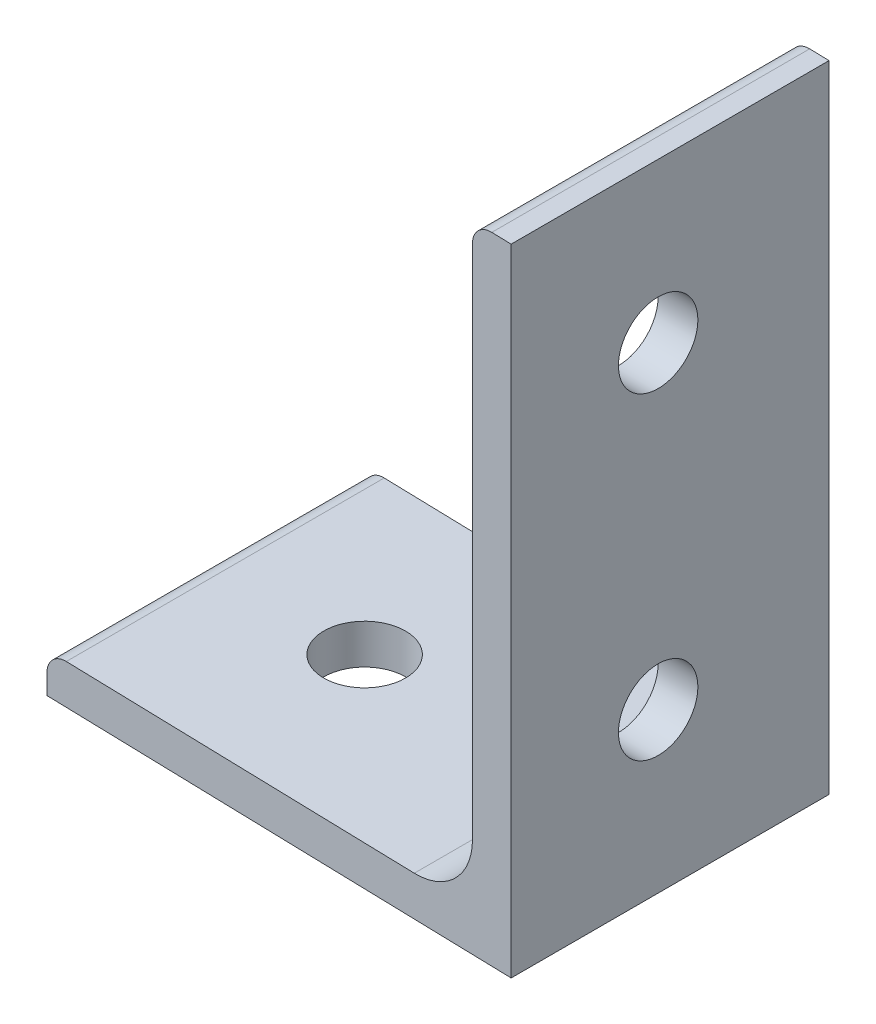
SolidWorks part; units mm, degrees
ref_plane "Front Plane" through (0, 0, 0) normal (0, 0, 1) x (1, 0, 0)
ref_plane "Top Plane" through (0, 0, 0) normal (0, 1, 0) x (1, 0, 0)
ref_plane "Right Plane" through (0, 0, 0) normal (1, 0, 0) x (0, 0, -1)
sketch "Sketch0" plane through (0, 0, 0) normal (0, 0, 1) x (1, 0, 0)
  line L0 (-19.05, -25.4) -> (19.05, -25.4)
  line L1 (19.05, -25.4) -> (19.05, 25.4)
  line L2 (19.05, 0) -> (0, 0) construction
  line L3 (0, 0) -> (0, -25.4) construction
  line L4 (15.875, -17.4498) -> (15.875, 25.4) construction
  line L5 (11.0998, -22.225) -> (-19.05, -22.225) construction
  arc A0 (15.875, -17.4498) -> (11.0998, -22.225) centre (11.0998, -17.4498) cw
  point P3 (14.4764, -20.8264)
  dimension "Inside Corner Radius" = 4.7752
  dimension "Outside Height" = 50.8
  dimension "Inside Height" = 47.625
  dimension "Inside Width" = 34.925
  dimension "Wall Thickness" = 3.175
  dimension "D1" = 3.175
  dimension "Outside Width" = 38.1
sketch "Sketch1" plane through (0, 0, 0) normal (1, 0, 0) x (0, 0, -1)
  line L0 (15.875, 0) -> (-15.875, 0)
  point P4 (0, 0)
  dimension "Length" = 31.75
sketch "Sketch2" plane through (0, 0, 0) normal (0, 0, 1) x (1, 0, 0)
  line L0 (-19.05, -25.4) -> (19.05, -25.4)
  line L1 (19.05, -25.4) -> (19.05, 25.4)
  line L2 (19.05, 25.4) -> (15.875, 25.4) construction
  line L3 (15.875, 23.8125) -> (15.875, -17.4498)
  line L4 (11.0998, -22.225) -> (-17.4625, -22.225)
  line L5 (-19.05, -25.4) -> (-19.05, -22.225) construction
  line L6 (17.4625, 25.4) -> (19.05, 25.4)
  line L7 (-19.05, -23.8125) -> (-19.05, -25.4)
  line L8 (19.05, 0) -> (0, 0) construction
  line L9 (0, 0) -> (0, -25.4) construction
  arc A0 (15.875, 23.8125) -> (17.4625, 25.4) centre (17.4625, 23.8125) cw
  arc A1 (-19.05, -23.8125) -> (-17.4625, -22.225) centre (-17.4625, -23.8125) cw
  arc A2 (15.875, -17.4498) -> (11.0998, -22.225) centre (11.0998, -17.4498) cw
  dimension "Inside Radius" = 4.7752
  dimension "Height" = 50.8
  dimension "Width" = 38.1
  dimension "Thickness" = 3.175
extrude "Boss-Extrude1" add sketch "Sketch2" along normal mid plane 31.75
sketch "Break Locations" plane through (0, 0, 0) normal (1, 0, 0) x (0, 0, -1)
  line L0 (35.941, 0) -> (-35.941, 0)
  line L1 (-15.875, -25.4) -> (-15.875, 25.4) construction
  line L2 (15.875, -25.4) -> (15.875, 25.4) construction
  point P0 (27.305, 0)
  point P1 (-27.305, 0)
  point P10 (0, 0)
  point P11 (-35.941, 0)
  point P13 (35.941, 0)
  dimension "D1" = 43.18
  dimension "D2" = 43.18
  dimension "D3" = 51.816
sketch "Sketch3" plane through (0, -25.4, 0) normal (0, -1, 0) x (1, 0, 0)
  line L1 (19.05, 15.875) -> (19.05, -15.875) construction
  line L2 (-19.05, 13.9268) -> (-19.05, -11.4819)
  line L6 (19.05, 0) -> (5.5904, 0) construction
  line L7 (19.05, -10.4842) -> (19.05, 14.9245)
  line L8 (-19.05, -11.4819) -> (19.05, -10.4842)
  line L10 (-19.05, 13.9268) -> (19.05, 14.9245)
sketch "Sketch4" plane through (19.05, 0, 0) normal (1, 0, 0) x (0, 0, -1)
  line L0 (-15.875, -25.4) -> (-3.175, -25.4) construction
  line L1 (-15.875, -25.4) -> (15.875, -25.4) construction
  line L2 (-3.175, -25.4) -> (-3.175, -12.7) construction
  line L3 (-3.175, -12.7) -> (-3.175, 12.7) construction
  circle A0 centre (-3.175, 12.7) radius 3.175
  circle A1 centre (-3.175, -12.7) radius 3.175
  dimension "D1" = 12.7
  dimension "D2" = 12.7
  dimension "D3" = 25.4
extrude "Cut-Extrude1" cut sketch "Sketch4" against normal through all
extrude "Cut-Extrude2" cut sketch "Sketch3" against normal through all flip side to cut
hole_wizard "1/4 Clearance Hole1" positions "Sketch7" profile "Sketch8" hole size "1/4" standard "ANSI Inch" end condition through all
sketch "Sketch7" plane through (0, -25.4, 0) normal (0, -1, 0) x (-1, 0, 0)
  point P4 (6.0219, -1.5636)
sketch "Sketch8" plane through (-6.0219, -25.4, 1.5636) normal (1, 0, 0) x (0, 0, -1)
  line L0 (0, 0) -> (0, 50.8)
  line L1 (0, 50.8) -> (3.2639, 50.8)
  line L2 (3.2639, 50.8) -> (3.2639, 0)
  line L5 (3.2639, 0) -> (0, 0)
  line L11 (0, -6.35) -> (0, 107.95) construction
  dimension "Thru Hole Dia." = 6.5278
  dimension "Thru Hole Depth" = 50.8
sketch "Sketch9" plane through (15.875, 0, 0) normal (-1, 0, 0) x (0, 0, 1)
  circle A0 centre (3.175, -12.7) radius 6.35
extrude "Cut-Extrude3" cut sketch "Sketch9" along normal blind 2.54
equation "\"D1@Break Locations\" = .85 * \"Height@Sketch2\""
equation "\"D2@Break Locations\"=\"D1@Break Locations\""
equation "\"Thickness@Sketch2\"=\"wall thickness@sketch0\""
equation "\"Height@Sketch2\"=\"outside height@sketch0\""
equation "\"Width@Sketch2\"=\"outside width@sketch0\""
equation "\"Inside Radius@Sketch2\"=\"inside corner radius@sketch0\""
equation "\"Length@Boss-Extrude1\"=\"length@sketch1\""
equation "\"D3@Break Locations\"=\"D2@Break Locations\"*1.2"
equation "\"D1@Sketch0\"=\"Wall Thickness@Sketch0\""
